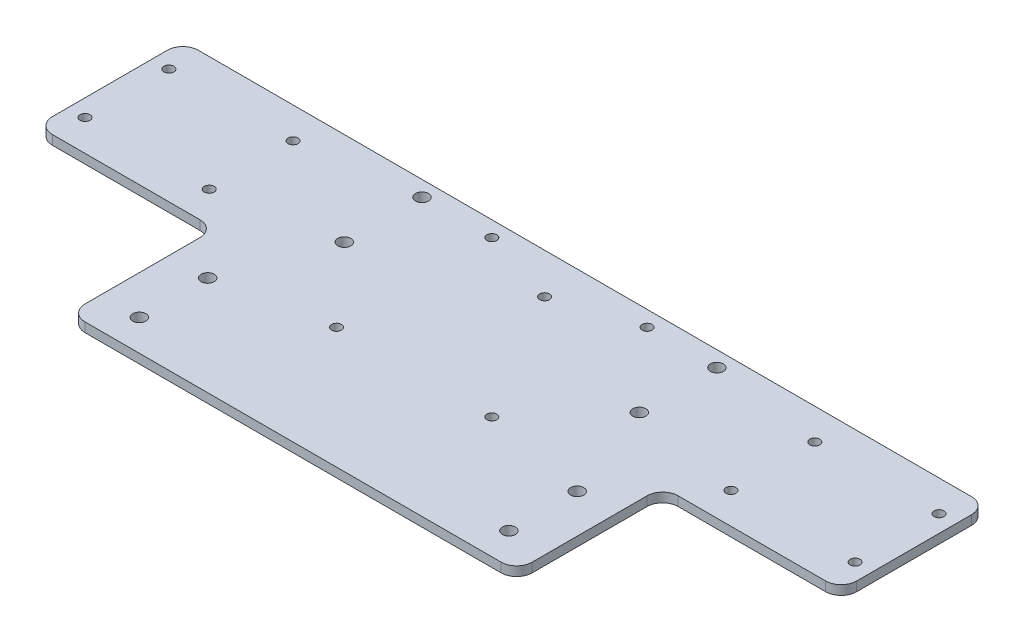
SolidWorks part; units mm, degrees
material "延性铁"
ref_plane "前视基准面" through (0, 0, 0) normal (0, 0, 1) x (1, 0, 0)
ref_plane "上视基准面" through (0, 0, 0) normal (0, 1, 0) x (1, 0, 0)
ref_plane "右视基准面" through (0, 0, 0) normal (1, 0, 0) x (0, 0, -1)
ref_plane "基准面4" through (0, 0, 0) normal (0, -1, 0) x (1, 0, 0)
sketch "草图1" plane through (0, 0, 0) normal (0, -1, 0) x (1, 0, 0)
  line L0 (-72, 0) -> (72, 0)
  line L1 (-129.5, -94) -> (129.5, -94)
  line L2 (170.3704, -70.5) -> (140.3704, -70.5) construction
  line L3 (-129.5, -47) -> (-72, -47)
  line L4 (-129.5, -47) -> (-129.5, -94)
  line L5 (72, 0) -> (72, -47)
  line L6 (129.5, -47) -> (129.5, -94)
  line L7 (129.5, -47) -> (72, -47)
  line L8 (-170.3704, -70.5) -> (-140.3704, -70.5) construction
  line L10 (-72, 0) -> (-72, -47)
  line L12 (0, 44.5655) -> (0, -175.9702) construction
  circle A0 centre (47.5, -89) radius 2.1
  circle A1 centre (-124, -84) radius 1.6
  circle A2 centre (-25, -89) radius 1.6
  circle A3 centre (-59.5, -32) radius 2.1
  circle A4 centre (-25, -39) radius 1.6
  circle A5 centre (84, -84) radius 1.6
  circle A7 centre (-59.5, -10) radius 2.1
  circle A8 centre (47.5, -64) radius 2.1
  circle A9 centre (-84, -57) radius 1.6
  circle A10 centre (-124, -57) radius 1.6
  circle A11 centre (-47.5, -64) radius 2.1
  circle A12 centre (-84, -84) radius 1.6
  circle A13 centre (124, -57) radius 1.6
  circle A14 centre (84, -57) radius 1.6
  circle A15 centre (59.5, -10) radius 2.1
  circle A17 centre (25, -39) radius 1.6
  circle A18 centre (59.5, -32) radius 2.1
  circle A19 centre (25, -89) radius 1.6
  circle A20 centre (124, -84) radius 1.6
  circle A21 centre (0, -81) radius 1.6
  circle A34 centre (-47.5, -89) radius 2.1
  point P27 (0, 0)
  point P56 (0, -94)
  dimension "D3" = 12.5
  dimension "D6" = 40
  dimension "D14" = 22
  dimension "D15" = 12.5
  dimension "D16" = 50
  dimension "D17" = 25
  dimension "D22" = 25
  dimension "D23" = 47
  dimension "D10" = 84
  dimension "D11" = 5
  dimension "D12" = 13
  dimension "D4" = 10
  dimension "D5" = 5.5
  dimension "D7" = 47.5
  dimension "D18" = 25
  dimension "D21" = 47.5
  dimension "D27" = 10
  dimension "D13" = 5
  dimension "D2" = 10
  dimension "D8" = 72
  dimension "D9" = 15
extrude "凸台-拉伸1" add sketch "草图1" against normal blind 3
fillet "圆角1" radius 5 8 edges at (72, 1.5, 0) (72, 1.5, -47) (129.5, 1.5, -47) (129.5, 1.5, -94) (-129.5, 1.5, -94) (-129.5, 1.5, -47) (-72, 1.5, -47) (-72, 1.5, 0) first distance on face at (72, 1.5, -23.5) first distance on face at (129.5, 1.5, -70.5) first distance on face at (-129.5, 1.5, -70.5) first distance on face at (-72, 1.5, -23.5)
